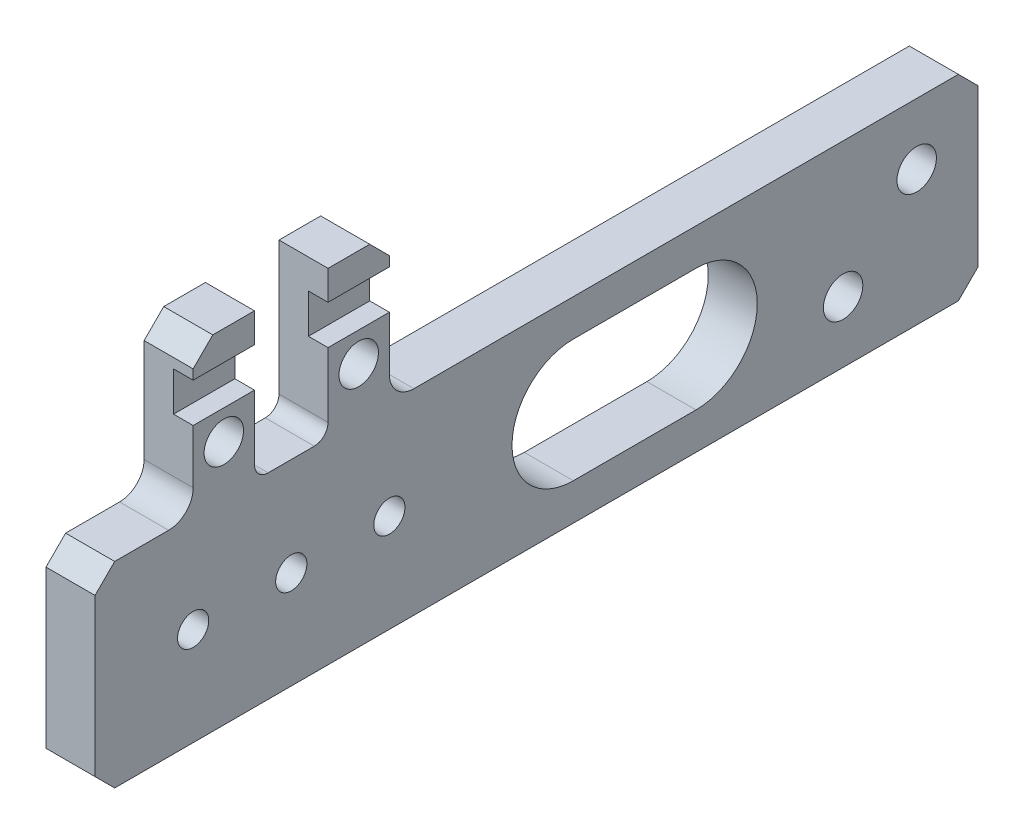
SolidWorks part; units mm, degrees
material "6061-T6 (SS)"
ref_plane "Front" through (0, 0, 0) normal (0, 0, 1) x (1, 0, 0)
ref_plane "Top" through (0, 0, 0) normal (0, 1, 0) x (1, 0, 0)
ref_plane "Right" through (0, 0, 0) normal (1, 0, 0) x (0, 0, -1)
sketch "Sketch1" plane through (0, 0, 0) normal (1, 0, 0) x (0, 0, -1)
  line L1 (0, 0) -> (114.3, 0)
  line L2 (0, 0) -> (0, 25.4)
  line L3 (0, 25.4) -> (9.525, 25.4)
  line L6 (114.3, 0) -> (114.3, 25.4)
  line L7 (38.1, 28.575) -> (38.1, 44.45)
  line L8 (38.1, 44.45) -> (30.1625, 44.45)
  line L9 (12.7, 44.45) -> (12.7, 28.575)
  line L10 (41.275, 25.4) -> (114.3, 25.4)
  line L11 (50.8, 25.4) -> (38.1, 44.45) construction
  line L12 (12.7, 44.45) -> (0, 25.4) construction
  line L14 (30.1625, 44.45) -> (30.1625, 27.178)
  line L15 (28.3845, 25.4) -> (22.4155, 25.4)
  line L16 (20.6375, 27.178) -> (20.6375, 44.45)
  line L17 (20.6375, 44.45) -> (12.7, 44.45)
  arc A0 (12.7, 28.575) -> (9.525, 25.4) centre (9.525, 28.575) cw
  arc A1 (38.1, 28.575) -> (41.275, 25.4) centre (41.275, 28.575) ccw
  arc A2 (22.4155, 25.4) -> (20.6375, 27.178) centre (22.4155, 27.178) cw
  arc A3 (30.1625, 27.178) -> (28.3845, 25.4) centre (28.3845, 27.178) cw
  point P14 (38.1, 25.4)
  dimension "D3" = 50.8
  dimension "D6" = 3.175
  dimension "D8" = 1.778
  dimension "D1" = 25.4
  dimension "D2" = 19.05
  dimension "D4" = 114.3
  dimension "D5" = 25.4
  dimension "D7" = 9.525
extrude "Boss-Extrude1" add sketch "Sketch1" along normal blind 6.35
hole_wizard "#10-32 Tapped Hole1" positions "Sketch2" profile "Sketch3" tap size "#10-32" standard "ANSI Inch" end condition through all
sketch "Sketch2" plane through (6.35, 0, 0) normal (1, 0, 0) x (0, 0, -1)
  line L0 (0, 0) -> (12.7, 12.7) construction
  line L1 (12.7, 12.7) -> (25.4, 12.7) construction
  line L2 (25.4, 12.7) -> (38.1, 12.7) construction
  line L3 (38.1, 12.7) -> (50.8, 25.4) construction
  line L4 (9.525, 25.4) -> (0, 25.4) construction
  line L6 (0, 25.4) -> (0, 0) construction
  point P0 (12.7, 12.7)
  point P2 (25.4, 12.7)
  point P4 (38.1, 12.7)
  dimension "D1" = 50.8
  dimension "D2" = 12.7
sketch "Sketch3" plane through (6.35, 12.7, -12.7) normal (0, 1, 0) x (0, 0, -1)
  line L0 (0, 0) -> (0, 6.35)
  line L1 (0, 6.35) -> (2.0193, 6.35)
  line L2 (2.0193, 6.35) -> (2.0193, 0)
  line L5 (2.0193, 0) -> (0, 0)
  line L11 (0, -6.35) -> (0, 107.95) construction
  dimension "Thru Tap Drill Dia." = 4.0386
  dimension "Thru Tap Drill Depth" = 6.35
cosmetic thread "Hole Thread1" parameters "D2"=4.826
cosmetic thread "Hole Thread2" parameters "D2"=4.826
cosmetic thread "Hole Thread3" parameters "D2"=4.826
hole_wizard "#10 Clearance Hole1" positions "Sketch4" profile "Sketch5" hole size "#10" standard "ANSI Inch" end condition through all
sketch "Sketch4" plane through (6.35, 0, 0) normal (1, 0, 0) x (0, 0, -1)
  line L0 (88.9, 0) -> (96.8375, 7.9375) construction
  line L1 (0, 0) -> (114.3, 0) construction
  line L2 (96.8375, 7.9375) -> (106.3625, 17.4625) construction
  line L3 (106.3625, 17.4625) -> (114.3, 25.4) construction
  line L5 (114.3, 0) -> (114.3, 25.4) construction
  line L6 (20.6375, 44.45) -> (16.6688, 31.75) construction
  line L7 (16.6688, 31.75) -> (12.7, 44.45) construction
  line L10 (30.1625, 44.45) -> (34.1313, 31.75) construction
  line L11 (34.1313, 31.75) -> (38.1, 44.45) construction
  line L13 (9.525, 25.4) -> (0, 25.4) construction
  point P13 (106.3625, 17.4625)
  point P15 (96.8375, 7.9375)
  point P37 (34.1313, 31.75)
  point P39 (16.6688, 31.75)
  dimension "D1" = 25.4
  dimension "D2" = 9.525
  dimension "D3" = 6.35
sketch "Sketch5" plane through (6.35, 17.4625, -106.3625) normal (0, 1, 0) x (0, 0, -1)
  line L0 (0, 0) -> (0, 6.35)
  line L1 (0, 6.35) -> (2.5527, 6.35)
  line L2 (2.5527, 6.35) -> (2.5527, 0)
  line L5 (2.5527, 0) -> (0, 0)
  line L11 (0, -6.35) -> (0, 107.95) construction
  dimension "Thru Hole Dia." = 5.1054
  dimension "Thru Hole Depth" = 6.35
sketch "Sketch6" plane through (6.35, 0, 0) normal (1, 0, 0) x (0, 0, -1)
  line L0 (12.7, 44.45) -> (12.7, 28.575) construction
  line L1 (12.7, 40.64) -> (38.1, 40.64)
  line L2 (12.7, 40.64) -> (12.7, 35.56)
  line L3 (12.7, 35.56) -> (38.1, 35.56)
  line L4 (38.1, 40.64) -> (38.1, 35.56)
  line L5 (38.1, 28.575) -> (38.1, 44.45) construction
  line L6 (9.525, 25.4) -> (0, 25.4) construction
  point P8 (12.7, 38.1)
  dimension "D1" = 5.08
  dimension "D2" = 12.7
extrude "Cut-Extrude1" cut sketch "Sketch6" against normal blind 2.54
chamfer "Chamfer1" distance 2.54 angle 45 6 edges at (3.175, 44.45, -38.1) (3.175, 44.45, -12.7) (3.175, 25.4, -114.3) (3.175, 0, -114.3) (3.175, 0, 0) (3.175, 25.4, 0)
sketch "Sketch7" plane through (6.35, 0, 0) normal (1, 0, 0) x (0, 0, -1)
  line L0 (61.9125, 12.7) -> (77.7875, 12.7) construction
  line L1 (61.9125, 20.6375) -> (77.7875, 20.6375)
  line L2 (61.9125, 4.7625) -> (77.7875, 4.7625)
  line L3 (0, 22.86) -> (0, 2.54) construction
  line L4 (114.3, 2.54) -> (114.3, 22.86) construction
  line L5 (2.54, 0) -> (111.76, 0) construction
  arc A0 (61.9125, 20.6375) -> (61.9125, 4.7625) centre (61.9125, 12.7) ccw
  arc A1 (77.7875, 4.7625) -> (77.7875, 20.6375) centre (77.7875, 12.7) ccw
  point P2 (69.85, 12.7)
  dimension "D1" = 15.875
  dimension "D2" = 53.975
  dimension "D3" = 28.575
  dimension "D4" = 12.7
extrude "Cut-Extrude2" cut sketch "Sketch7" against normal through all
